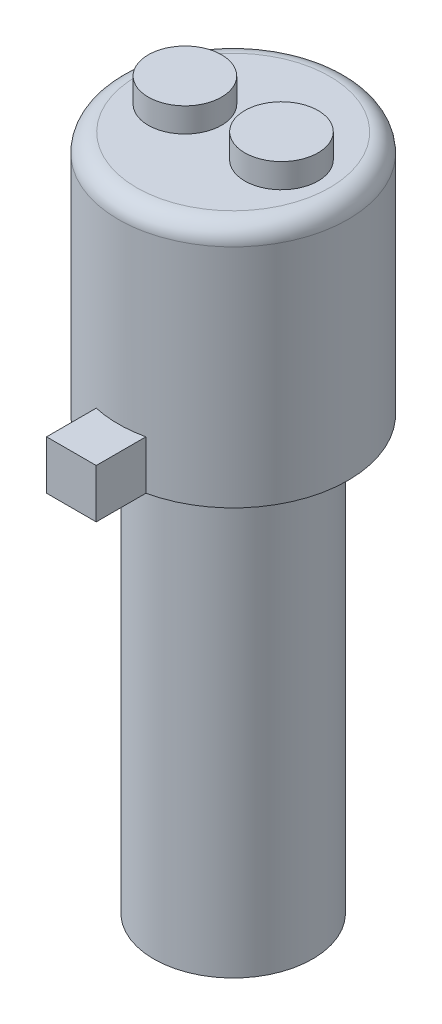
SolidWorks part; units mm, degrees
ref_plane "Front Plane" through (0, 0, 0) normal (0, 0, 1) x (1, 0, 0)
ref_plane "Top Plane" through (0, 0, 0) normal (0, 1, 0) x (1, 0, 0)
ref_plane "Right Plane" through (0, 0, 0) normal (1, 0, 0) x (0, 0, -1)
sketch "Sketch1" plane through (0, 0, 0) normal (0, 1, 0) x (1, 0, 0)
  circle A0 centre (0, 0) radius 3.25
  dimension "D1" = 6.5
extrude "Boss-Extrude1" add sketch "Sketch1" along normal blind 17.686 contours A0
sketch "Sketch2" plane through (0, 0, 0) normal (0, -1, 0) x (1, 0, 0)
  circle A1 centre (0, 0) radius 1.75
  dimension "D1" = 3.5
extrude "Cut-Extrude1" [suppressed] cut sketch "Sketch2" against normal blind 2.5
sketch "Sketch6" plane through (0, 17.686, 0) normal (0, 1, 0) x (1, 0, 0)
  circle A0 centre (0, 0) radius 4.7
  dimension "D1" = 9.4
extrude "Boss-Extrude2" add sketch "Sketch6" along normal blind 10 contours A0
fillet "Fillet2" radius 0.75 1 edges at (0, 27.686, 4.7)
sketch "Sketch7" plane through (0, 27.686, 0) normal (0, 1, 0) x (1, 0, 0)
  line L0 (3.95, 0) -> (0, 0) construction
  line L1 (0, 0) -> (-3.95, 0) construction
  line L2 (0, 0) -> (1.975, 0) construction
  line L3 (0, 0) -> (-1.975, 0) construction
  circle A0 centre (0, 0) radius 3.95 construction
  circle A1 centre (-1.975, 0) radius 1.5
  circle A2 centre (1.975, 0) radius 1.5
  dimension "D1" = 3
  dimension "D2" = 3
extrude "Boss-Extrude3" add sketch "Sketch7" along normal blind 1
sketch "Sketch8" plane through (0, 17.686, 0) normal (0, -1, 0) x (1, 0, 0)
  line L0 (0, 4.7) -> (0, -4.7) construction
  line L1 (-1.016, 4.5889) -> (-1.016, 6.6209)
  line L2 (-1.016, 6.6209) -> (1.016, 6.6209)
  line L3 (1.016, 6.6209) -> (1.016, 4.5889)
  circle A0 centre (0, 0) radius 4.7 construction
  arc A1 (1.016, 4.5889) -> (-1.016, 4.5889) centre (0, 0) ccw
  point P8 (0, 0)
  dimension "D1" = 2.032
  dimension "D2" = 2.032
extrude "Boss-Extrude4" add sketch "Sketch8" against normal blind 2
